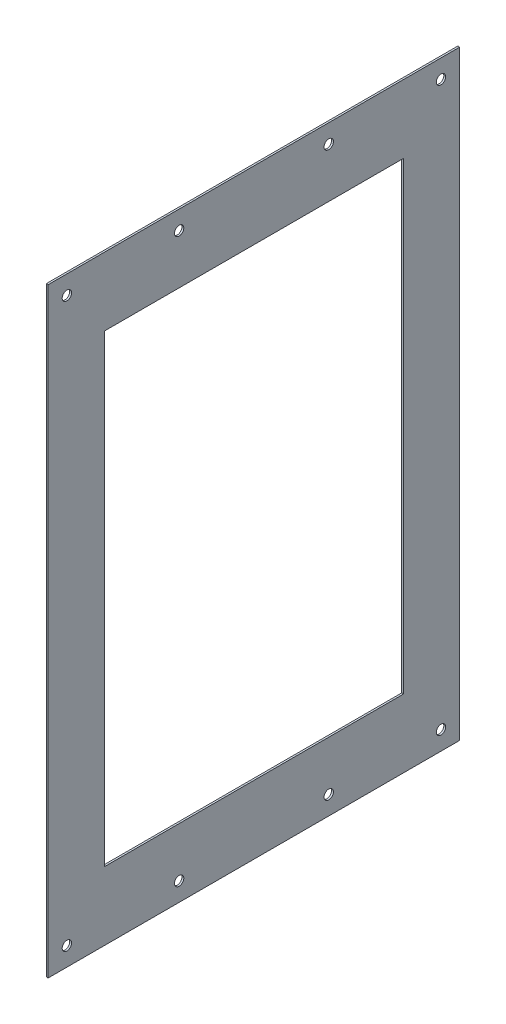
SolidWorks part; units mm, degrees
ref_plane "Front Plane" through (0, 0, 0) normal (1, 0, 0) x (0, 1, 0)
ref_plane "Top Plane" through (0, 0, 0) normal (0, 0, 1) x (0, 1, 0)
ref_plane "Right Plane" through (0, 0, 0) normal (0, 1, 0) x (-1, 0, 0)
sketch "Sketch1" plane through (0, 0, 0) normal (1, 0, 0) x (0, 1, 0)
  line L1 (-160.5, -110) -> (160.5, -110)
  line L2 (-160.5, -110) -> (-160.5, 110)
  line L3 (-160.5, 110) -> (160.5, 110)
  line L4 (160.5, -110) -> (160.5, 110)
  line L5 (-160.5, -110) -> (160.5, 110) construction
  line L6 (-160.5, 110) -> (160.5, -110) construction
  point P0 (0, 0)
  dimension "D1" = 321
  dimension "D2" = 220
extrude "Boss-Extrude1" add sketch "Sketch1" along normal blind 1
sketch "Sketch2" plane through (1, 0, 0) normal (1, 0, 0) x (0, 1, 0)
  line L0 (0, 110) -> (0, -110) construction
  line L1 (160.5, 110) -> (-160.5, 110) construction
  line L2 (-160.5, -110) -> (160.5, -110) construction
  line L4 (160.5, -110) -> (160.5, 110) construction
  line L5 (160.5, 0) -> (-160.5, 0) construction
  line L6 (-160.5, 110) -> (-160.5, -110) construction
  circle A0 centre (-150.5, 100) radius 2.5
  circle A1 centre (150.5, 100) radius 2.5
  circle A2 centre (-150.5, -100) radius 2.5
  circle A3 centre (150.5, -100) radius 2.5
  dimension "D1" = 5
  dimension "D2" = 10
  dimension "D3" = 10
extrude "Cut-Extrude1" cut sketch "Sketch2" against normal through all
sketch "Sketch3" plane through (1, 0, 0) normal (1, 0, 0) x (0, 1, 0)
  line L1 (-124, -80) -> (124, -80)
  line L2 (-124, -80) -> (-124, 80)
  line L3 (-124, 80) -> (124, 80)
  line L4 (124, -80) -> (124, 80)
  line L5 (-124, -80) -> (124, 80) construction
  line L6 (-124, 80) -> (124, -80) construction
  point P0 (0, 0)
  dimension "D1" = 248
  dimension "D2" = 160
extrude "Cut-Extrude2" cut sketch "Sketch3" against normal through all
sketch "Sketch4" plane through (1, 0, 0) normal (1, 0, 0) x (0, 1, 0)
  line L0 (0, 80) -> (0, -80) construction
  line L1 (124, 80) -> (-124, 80) construction
  line L2 (-124, -80) -> (124, -80) construction
  line L3 (-160.5, 110) -> (-160.5, -110) construction
  line L4 (124, -80) -> (124, 80) construction
  line L5 (124, 0) -> (-124, 0) construction
  line L6 (-124, 80) -> (-124, -80) construction
  circle A0 centre (-150.5, 40) radius 2.5
  circle A2 centre (150.5, 40) radius 2.5
  circle A3 centre (-150.5, -40) radius 2.5
  circle A4 centre (150.5, -40) radius 2.5
  dimension "D1" = 5
  dimension "D2" = 10
  dimension "D3" = 40
extrude "Cut-Extrude3" cut sketch "Sketch4" against normal through all
